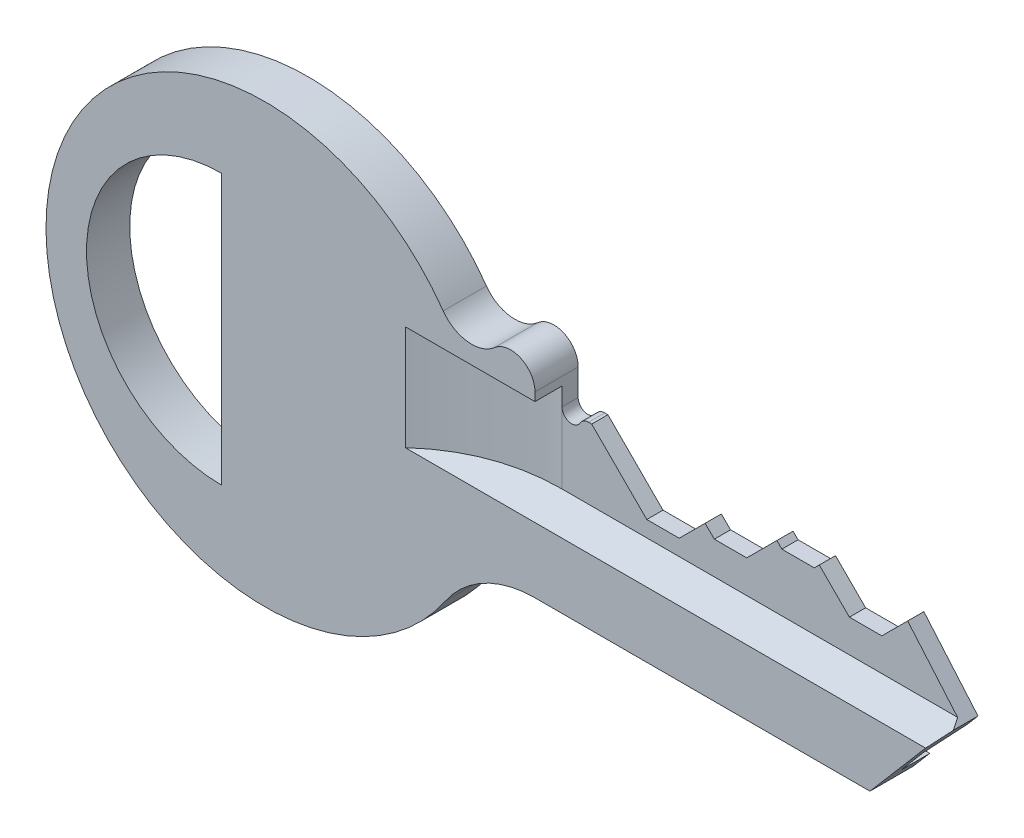
SolidWorks part; units mm, degrees
material "Brass"
ref_plane "Front" through (0, 0, 0) normal (0, 0, 1) x (1, 0, 0)
ref_plane "Top" through (0, 0, 0) normal (0, 1, 0) x (1, 0, 0)
ref_plane "Right" through (0, 0, 0) normal (1, 0, 0) x (0, 0, -1)
sketch "Sketch1" plane through (0, 0, 0) normal (0, 0, 1) x (1, 0, 0)
  line L8 (0, 0) -> (15.748, 0)
  line L9 (15.748, 0) -> (18.796, 3.5687)
  line L11 (18.796, 3.5687) -> (15.748, 7.1374)
  line L12 (0, 7.1374) -> (0, 8.382)
  line L17 (15.748, 7.1374) -> (1.2491, 7.1374)
  line L27 (-14.732, 9.9187) -> (-14.732, -2.7813)
  line L28 (1.6105, 6.6802) -> (-0.587, 6.6802) construction
  arc A1 (-4.3128, 9.525) -> (-4.1961, -2.2197) centre (-12.7, 3.5687) ccw
  arc A3 (0, 0) -> (-4.1961, -2.2197) centre (0, -5.0759) ccw
  arc A4 (0, 7.1374) -> (0.8531, 6.9088) centre (0.4572, 7.1374) ccw
  arc A5 (0, 8.382) -> (-1.8964, 9.2415) centre (-1.143, 8.382) ccw
  arc A6 (-1.8964, 9.2415) -> (-4.3128, 9.525) centre (-2.9767, 10.4739) cw
  arc A8 (-14.732, -2.7813) -> (-14.732, 9.9187) centre (-14.732, 3.5687) cw
  arc A10 (0.8531, 6.9088) -> (1.2491, 7.1374) centre (1.2491, 6.6802) cw
  point P9 (-22.987, 3.5687)
  point P22 (-1.143, 9.525)
  point P41 (-21.082, 3.5687)
  dimension "D6" = 9.525
  dimension "D7" = 6.6802
  dimension "D8" = 10.287
  dimension "D19" = 1.143
  dimension "D20" = 6.35
  dimension "D2" = 7.1374
  dimension "D3" = 41.783
  dimension "D4" = 18.796
  dimension "D5" = 15.748
  dimension "D21" = 1.905
extrude "Boss-Extrude1" add sketch "Sketch1" along normal blind 2.032
ref_plane "Plane1" through (18.796, 0, 0) normal (1, 0, 0) x (0, 0, -1)
sketch "Sketch2" plane through (18.796, 0, 0) normal (1, 0, 0) x (0, 0, -1)
  line L0 (0, 0) -> (0, 0.9144) construction
  line L1 (0, 0) -> (0, 3.5687) construction
  line L2 (0, 0.9144) -> (-1.3589, 0.9144)
  line L3 (-1.3589, 0.9144) -> (-1.3589, 2.1844)
  line L4 (-1.3589, 2.1844) -> (0, 2.969)
  line L7 (0, 3.5687) -> (0, 7.1374) construction
  line L10 (-0.762, 3.7973) -> (-2.032, 3.0641)
  line L11 (-2.032, 0) -> (-2.032, 3.5687) construction
  line L12 (-2.032, 3.0641) -> (-2.032, 0) construction
  line L13 (-2.032, 0) -> (0, 0) construction
  line L14 (0, 2.969) -> (0, 0.9144)
  line L22 (-2.032, 3.0641) -> (-2.032, 7.9883)
  line L23 (-2.032, 7.9883) -> (-0.762, 7.9883)
  line L25 (-0.762, 7.9883) -> (-0.762, 3.7973)
  dimension "D1" = 0.9144
  dimension "D2" = 1.27
  dimension "D3" = 3.7973
  dimension "D4" = 30
  dimension "D5" = 0.762
  dimension "D6" = 0.6731
  dimension "D7" = 4.191
extrude "Cut-Extrude2" cut sketch "Sketch2" against normal blind 24.892
fillet "Fillet1" radius 15.24 2 edges at (-6.096, 1.5494, 1.3589) (-6.096, 5.8928, 0.762)
sketch "Sketch3" plane through (0, 0, 0.762) normal (0, 0, 1) x (1, 0, 0)
  line L1 (18.796, 7.9883) -> (18.796, 3.5687)
  line L3 (0, 0) -> (15.748, 0) construction
  line L4 (-6.096, 7.9883) -> (-0.0053, 7.9883) construction
  line L6 (0, 7.9883) -> (0, 7.1374) construction
  line L7 (15.748, 7.1374) -> (18.6008, 3.7973) construction
  line L8 (0.5461, 7.9883) -> (18.796, 7.9883)
  line L36 (16.2511, 6.5483) -> (15.0368, 5.334)
  line L37 (15.0368, 5.334) -> (13.5128, 5.334)
  line L38 (13.5128, 5.334) -> (12.0967, 6.7501)
  line L39 (12.0967, 6.7501) -> (11.8618, 6.5151)
  line L40 (11.8618, 6.5151) -> (10.3378, 6.5151)
  line L41 (10.3378, 6.5151) -> (10.1028, 6.7501)
  line L42 (10.1028, 6.7501) -> (8.6868, 5.334)
  line L43 (8.6868, 5.334) -> (7.1628, 5.334)
  line L44 (7.1628, 5.334) -> (6.731, 5.7658)
  line L45 (6.731, 5.7658) -> (5.5118, 4.5466)
  line L46 (5.5118, 4.5466) -> (3.9878, 4.5466)
  line L47 (3.9878, 4.5466) -> (0.5461, 7.9883)
  line L53 (18.796, 3.5687) -> (16.2511, 6.5483)
  point P18 (7.9248, 5.334)
  point P24 (4.7498, 4.5466)
  point P25 (11.0998, 6.5151)
  point P26 (14.2748, 5.334)
  dimension "Cut3" = 6.5151
  dimension "Cut2" = 5.334
  dimension "Cut1" = 4.5466
  dimension "D5" = 1.524
  dimension "D7" = 90
  dimension "D8" = 4.7498
  dimension "D9" = 7.9248
  dimension "D10" = 11.0998
  dimension "D11" = 14.2748
  dimension "D6" = 135
  dimension "Cut4" = 5.334
extrude "Cut-Extrude3" cut sketch "Sketch3" against normal through all
equation "\"0\"= .2720"
equation "\"1\"= .2565"
equation "\"2\"= .2410"
equation "\"3\"= .2255"
equation "\"4\"= .2100"
equation "\"5\"= .1945"
equation "\"6\"= .1790"
equation "\"7\"= .1635"
equation "\"Cut1@Sketch3\"=\"6\""
equation "\"Cut2@Sketch3\"=\"4\""
equation "\"Cut3@Sketch3\"=\"1\""
equation "\"Cut4@Sketch3\"=\"4\""
